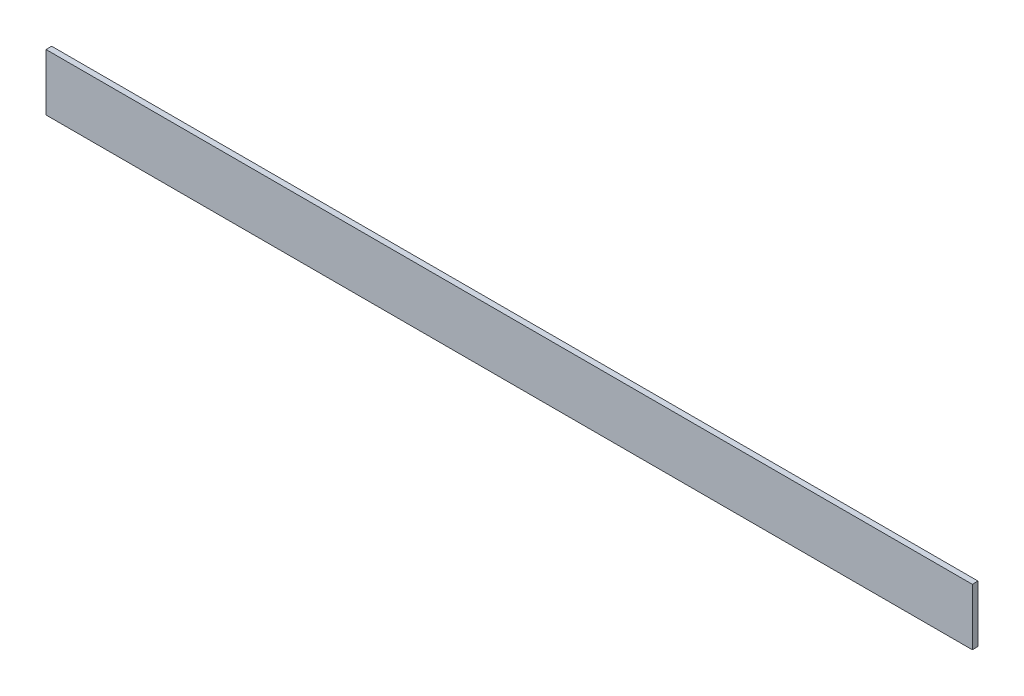
SolidWorks part; units mm, degrees
ref_plane "Спереди" through (0, 0, 0) normal (0, 0, 1) x (1, 0, 0)
ref_plane "Сверху" through (0, 0, 0) normal (0, 1, 0) x (1, 0, 0)
ref_plane "Справа" through (0, 0, 0) normal (1, 0, 0) x (0, 0, -1)
sketch "Эскиз1" plane through (0, 0, 0) normal (1, 0, 0) x (0, 0, -1)
  line L0 (0, 0) -> (30, 0)
  line L1 (0, 0) -> (0, 30)
extrude "Вытянуть-Тонкостенный1" add sketch "Эскиз1" along normal blind 490 thin thin type one direction wall 3
sketch "Эскиз2" plane through (0, 0, 0) normal (0, -1, 0) x (1, 0, 0)
  line L1 (0, -30) -> (27, -30)
  line L2 (0, -30) -> (0, -3)
  line L3 (0, -3) -> (27, -3)
  line L4 (27, -30) -> (27, -3)
  line L5 (490, -30) -> (463, -30)
  line L6 (490, -30) -> (490, -3)
  line L7 (490, -3) -> (463, -3)
  line L8 (463, -30) -> (463, -3)
extrude "Вырез-Вытянуть1" cut sketch "Эскиз2" against normal through all
